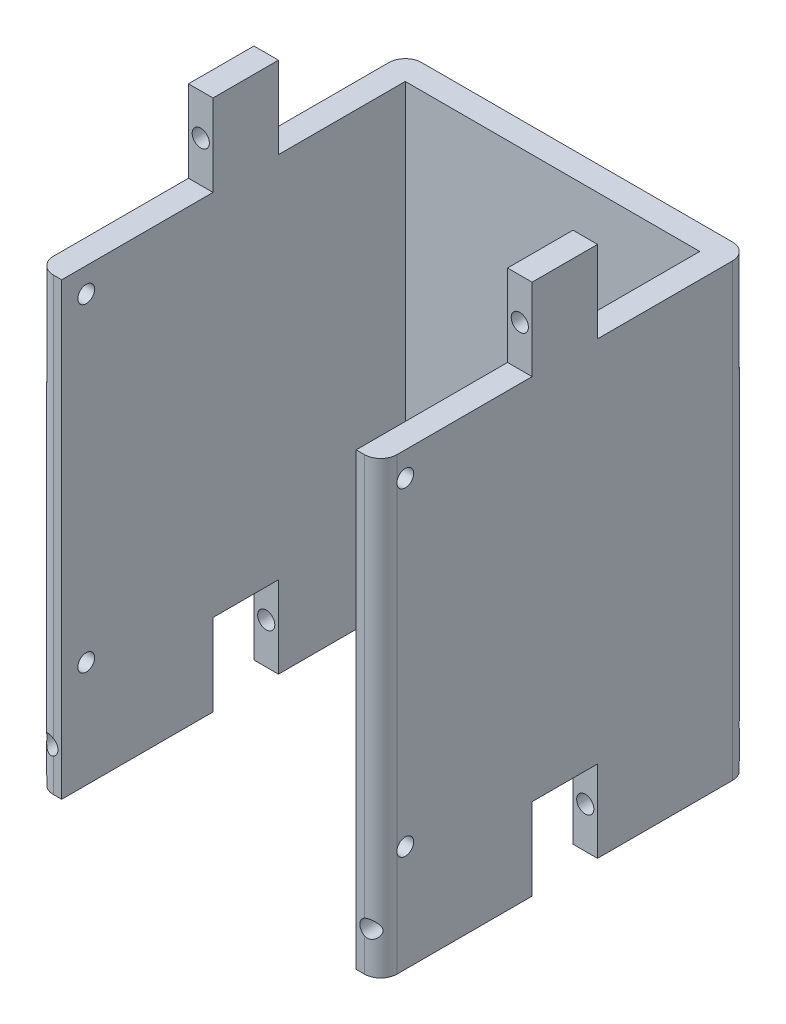
SolidWorks part; units mm, degrees
ref_plane "前基準面" through (0, 0, 0) normal (0, 0, 1) x (1, 0, 0)
ref_plane "上基準面" through (0, 0, 0) normal (0, 1, 0) x (1, 0, 0)
ref_plane "右基準面" through (0, 0, 0) normal (1, 0, 0) x (0, 0, -1)
sketch "草圖1" plane through (0, 0, 0) normal (0, 0, 1) x (1, 0, 0)
  line L0 (-14.5455, -28.0909) -> (-15.5455, -28.0909)
  line L1 (-14.5455, 16.9091) -> (25.4545, 16.9091)
  line L3 (-14.5455, -28.0909) -> (25.4545, -28.0909)
  line L5 (-15.5455, -28.0909) -> (-15.5455, 16.9091)
  line L6 (-15.5455, 16.9091) -> (-14.5455, 16.9091)
  line L8 (26.4545, -28.0909) -> (26.4545, 16.9091)
  line L9 (26.4545, 16.9091) -> (25.4545, 16.9091)
  line L10 (26.4545, -28.0909) -> (25.4545, -28.0909)
  dimension "D1" = 40
  dimension "D2" = 45
  dimension "D3" = 1
  dimension "D4" = 1
extrude "填料-伸長1" add sketch "草圖1" along normal blind 40 and the other way blind 5 contours L3 L10 L8 L9 L1 L6 L5 L0
sketch "草圖2" plane through (0, 16.9091, 0) normal (0, 1, 0) x (1, 0, 0)
  line L0 (5.4545, 5) -> (5.4545, -40.6532) construction
  line L1 (-15.5455, 5) -> (26.4545, 5) construction
  line L2 (-15.5455, -40) -> (26.4545, -40) construction
  line L3 (-12.5455, -3) -> (23.4545, -3)
  line L4 (-12.5455, -3) -> (-12.5455, -40)
  line L5 (-12.5455, -40) -> (23.4545, -40)
  line L6 (23.4545, -3) -> (23.4545, -40)
  dimension "D3" = 37
extrude "除料-伸長1" cut sketch "草圖2" against normal blind 50
sketch "草圖5" plane through (0, 16.9091, 0) normal (0, 1, 0) x (1, 0, 0)
  line L1 (-12.5455, -3) -> (23.4545, -3)
  line L2 (-12.5455, -3) -> (-12.5455, 2)
  line L3 (-12.5455, 2) -> (23.4545, 2)
  line L4 (23.4545, -3) -> (23.4545, 2)
  dimension "D1" = 36
  dimension "D2" = 5
extrude "除料-伸長4" cut sketch "草圖5" against normal blind 43
ref_plane "平面1" through (0, 16.9091, 0) normal (0, 1, 0) x (1, 0, 0)
ref_plane "平面2" through (0, -28.0909, 0) normal (0, -1, 0) x (-1, 0, 0)
ref_plane "平面4" through (-15.5455, 0, 0) normal (-1, 0, 0) x (0, 0, 1)
sketch "草圖9" plane through (-15.5455, 0, 0) normal (-1, 0, 0) x (0, 0, 1)
  line L3 (-5, -28.0909) -> (40, -28.0909) construction
  line L4 (40, -28.0909) -> (40, 16.9091) construction
  line L5 (-5, 16.9091) -> (40, 16.9091) construction
  circle A2 centre (37, -25.0909) radius 1.025
  circle A3 centre (37, 13.9091) radius 1.025
  dimension "D1" = 2.05
  dimension "D2" = 2.05
  dimension "D3" = 3
  dimension "D4" = 3
  dimension "D5" = 3
  dimension "D6" = 3
extrude "除料-伸長5" cut sketch "草圖9" against normal blind 45.5
sketch "草圖10" plane through (0, 16.9091, 0) normal (0, 1, 0) x (1, 0, 0)
  line L0 (5.4545, -3) -> (5.4545, 10.5844) construction
  line L1 (-12.5455, -3) -> (23.4545, -3) construction
  line L5 (-15.5455, -17.5) -> (26.4545, -17.5) construction
  line L6 (-15.5455, 24.75) -> (-15.5455, -24.75) construction
  line L7 (26.4545, 5) -> (26.4545, -40) construction
  line L8 (-15.5455, 5) -> (26.4545, 5) construction
  line L10 (-12.5455, 2) -> (-12.5455, -40) construction
  line L11 (-15.5455, -13.5) -> (-12.5455, -13.5)
  line L12 (-15.5455, -13.5) -> (-15.5455, -21.5)
  line L13 (-15.5455, -21.5) -> (-12.5455, -21.5)
  line L14 (-12.5455, -13.5) -> (-12.5455, -21.5)
  line L15 (26.4545, -21.5) -> (23.4545, -21.5)
  line L16 (23.4545, -13.5) -> (23.4545, -21.5)
  line L17 (26.4545, -13.5) -> (23.4545, -13.5)
  line L18 (26.4545, -13.5) -> (26.4545, -21.5)
  dimension "D1" = 22.5
  dimension "D2" = 4
  dimension "D3" = 3
  dimension "D4" = 4
extrude "填料-伸長4" add sketch "草圖10" along normal blind 10
sketch "草圖11" plane through (0, -28.0909, 0) normal (0, -1, 0) x (-1, 0, 0)
  line L0 (-26.4545, -17.5) -> (15.8441, -17.5) construction
  line L1 (-26.4545, 5) -> (-26.4545, -40) construction
  line L2 (-26.4545, 5) -> (15.5455, 5) construction
  line L3 (-5.4545, 5) -> (-5.4545, -41.7705) construction
  line L4 (-26.4545, -40) -> (-23.4545, -40)
  line L5 (-26.4545, -13.5) -> (-23.4545, -13.5)
  line L6 (-26.4545, -13.5) -> (-26.4545, 5)
  line L7 (-26.4545, 5) -> (-23.4545, 5)
  line L8 (-23.4545, -13.5) -> (-23.4545, 5)
  line L9 (-23.4545, -21.5) -> (-23.4545, -40)
  line L10 (-26.4545, -21.5) -> (-23.4545, -21.5)
  line L11 (-26.4545, -21.5) -> (-26.4545, -40)
  line L12 (15.5455, -21.5) -> (15.5455, -40)
  line L13 (15.5455, -21.5) -> (12.5455, -21.5)
  line L14 (12.5455, -21.5) -> (12.5455, -40)
  line L15 (15.5455, -40) -> (12.5455, -40)
  line L16 (15.5455, 5) -> (12.5455, 5)
  line L17 (12.5455, -13.5) -> (12.5455, 5)
  line L18 (15.5455, -13.5) -> (12.5455, -13.5)
  line L19 (15.5455, -13.5) -> (15.5455, 5)
  dimension "D1" = 22.5
  dimension "D2" = 21
  dimension "D3" = 3
  dimension "D4" = 4
extrude "填料-伸長5" add sketch "草圖11" along normal blind 10
ref_plane "平面5" through (0, 0, 13.5) normal (0, 0, -1) x (-1, 0, 0)
sketch "草圖12" plane through (0, 0, 13.5) normal (0, 0, -1) x (-1, 0, 0)
  line L0 (-24.9545, 26.9091) -> (-24.9545, 15.9652) construction
  line L1 (-26.4545, 26.9091) -> (-23.4545, 26.9091) construction
  line L2 (-26.4545, 21.9091) -> (15.5455, 21.9091) construction
  line L3 (-26.4545, 26.9091) -> (-26.4545, 16.9091) construction
  line L4 (15.5455, -24.75) -> (15.5455, 24.75) construction
  line L5 (-5.4545, 21.9091) -> (-5.4545, -4.7924) construction
  circle A0 centre (-24.9545, 21.9091) radius 1.05
  circle A1 centre (14.0455, 21.9091) radius 1.05
  dimension "D1" = 2.1
extrude "除料-伸長6" cut sketch "草圖12" against normal blind 10
ref_plane "平面6" through (0, 0, -5) normal (0, 0, -1) x (-1, 0, 0)
sketch "草圖13" plane through (0, 0, -5) normal (0, 0, -1) x (-1, 0, 0)
  line L0 (-26.4545, -33.0909) -> (15.5455, -33.0909) construction
  line L1 (-26.4545, -38.0909) -> (-26.4545, 16.9091) construction
  line L2 (15.5455, -24.75) -> (15.5455, 24.75) construction
  line L3 (-24.9545, -38.0909) -> (-24.9545, -17.409) construction
  line L4 (-23.4545, -38.0909) -> (-26.4545, -38.0909) construction
  line L5 (-5.4545, -33.0909) -> (-5.4545, 7.1098) construction
  circle A0 centre (-24.9545, -33.0909) radius 1.05
  circle A1 centre (14.0455, -33.0909) radius 1.05
  dimension "D2" = 2.1
  dimension "D1" = 5
extrude "除料-伸長7" cut sketch "草圖13" against normal blind 63.5
fillet "圓角4" radius 2 1 edges at (26.4545, -10.5909, -5)
fillet "圓角5" radius 2 1 edges at (-15.5455, -10.5909, -5)
fillet "圓角6" radius 2 1 edges at (26.4545, -10.5909, 40)
fillet "圓角7" radius 2 1 edges at (-15.5455, -10.5909, 40)
